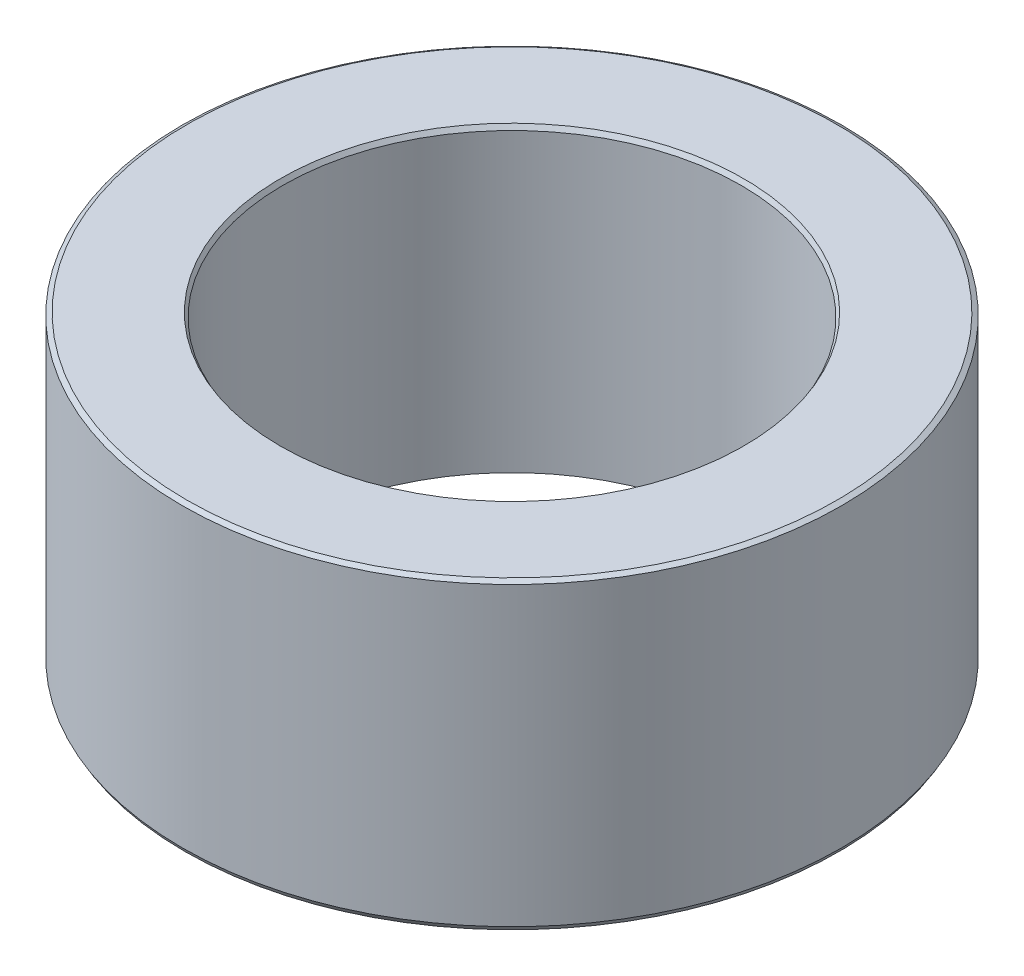
SolidWorks part; units mm, degrees
ref_plane "Front Plane" through (0, 0, 0) normal (0, 0, 1) x (1, 0, 0)
ref_plane "Top Plane" through (0, 0, 0) normal (0, 1, 0) x (1, 0, 0)
ref_plane "Right Plane" through (0, 0, 0) normal (1, 0, 0) x (0, 0, -1)
sketch "Sketch1" plane through (0, 0, 0) normal (0, 1, 0) x (1, 0, 0)
  circle A0 centre (0, 0) radius 52.5
  dimension "SLEEVE_OD" = 105
extrude "Boss-Extrude1" add sketch "Sketch1" along normal blind 48.3163
sketch "Sketch2" plane through (0, 0, 0) normal (0, 1, 0) x (1, 0, 0)
  circle A0 centre (0, 0) radius 36.4793
  dimension "BORE_D" = 72.9587
extrude "Cut-Extrude1" cut sketch "Sketch2" along normal through all
chamfer "Chamfer1" distance 0.4132 angle 60 4 edges at (0, 48.3163, 36.4793) (0, 0, 36.4793) (0, 0, 52.5) (0, 48.3163, 52.5) first distance on face at (0, 48.3163, 36.4793) first distance on face at (0, 0, 36.4793) first distance on face at (0, 48.3163, 52.5)
